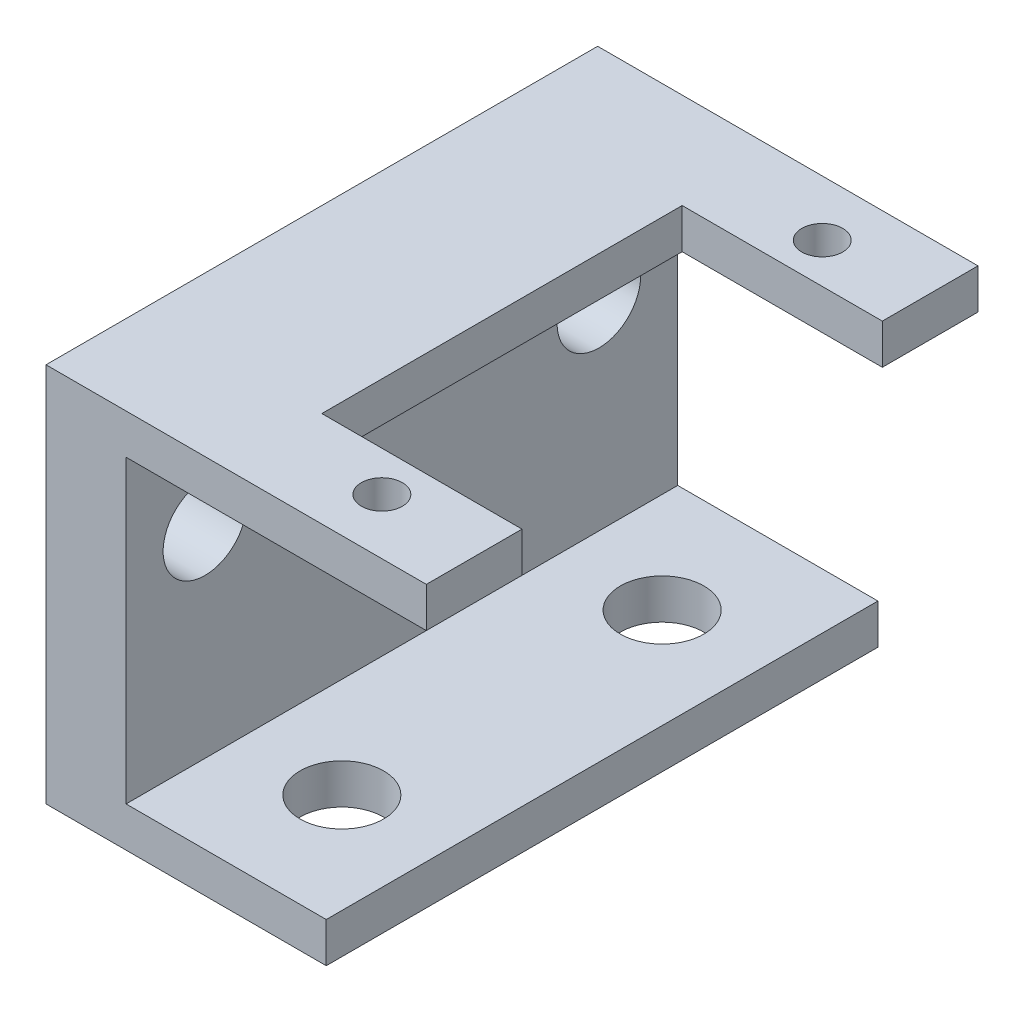
SolidWorks part; units mm, degrees
ref_plane "Front Plane" through (0, 0, 0) normal (0, 0, 1) x (1, 0, 0)
ref_plane "Top Plane" through (0, 0, 0) normal (0, 1, 0) x (1, 0, 0)
ref_plane "Right Plane" through (0, 0, 0) normal (1, 0, 0) x (0, 0, -1)
sketch "Sketch1" plane through (0, 0, 0) normal (0, 0, 1) x (1, 0, 0)
  line L1 (0, 0) -> (17.78, 0)
  line L2 (0, 0) -> (0, 2.54)
  line L3 (0, 2.54) -> (17.78, 2.54)
  line L4 (17.78, 0) -> (17.78, 2.54)
  line L5 (0, 2.54) -> (5.08, 2.54)
  line L6 (0, 2.54) -> (0, 21.59)
  line L7 (0, 21.59) -> (5.08, 21.59)
  line L8 (5.08, 2.54) -> (5.08, 21.59)
  line L9 (0, 21.59) -> (24.13, 21.59)
  line L10 (0, 21.59) -> (0, 24.13)
  line L11 (0, 24.13) -> (24.13, 24.13)
  line L12 (24.13, 21.59) -> (24.13, 24.13)
  dimension "D1" = 5.08
  dimension "D2" = 12.7
  dimension "D3" = 19.05
  dimension "D4" = 2.54
  dimension "D5" = 2.54
  dimension "D6" = 19.05
extrude "Boss-Extrude1" add sketch "Sketch1" along normal blind 35 contours L9 L12 L11 L10 L7 | L6 L5 L8 L7 | L2 L1 L4 L3 region at (12.065, 22.86, 0)
hole_wizard "Ø5.0mm Dowel Hole1" positions "Sketch2" profile "Sketch3" hole size "Ø5.0" standard "ANSI Metric" end condition through all
sketch "Sketch2" plane through (5.08, 0, 0) normal (1, 0, 0) x (0, 0, -1)
  line L3 (-35, 2.54) -> (0, 2.54) construction
  line L6 (-30, 15.24) -> (-5, 15.24) construction
  line L8 (-35, 0) -> (0, 0) construction
  point P0 (-30, 15.24)
  point P2 (-5, 15.24)
  point P30 (-17.5, 0)
  point P31 (-17.5, 15.24)
  dimension "D1" = 25
  dimension "D3" = 12.7
sketch "Sketch3" plane through (5.08, 15.24, 30) normal (0, 1, 0) x (0, 0, -1)
  line L0 (0, 0) -> (0, 5.08)
  line L1 (0, 5.08) -> (2.65, 5.08)
  line L2 (2.65, 5.08) -> (2.65, 0)
  line L5 (2.65, 0) -> (0, 0)
  line L11 (0, -6.35) -> (0, 107.95) construction
  dimension "Thru Hole Dia." = 5.3
  dimension "Thru Hole Depth" = 5.08
hole_wizard "Ø5.0mm Dowel Hole2" positions "Sketch4" profile "Sketch5" hole size "Ø5.0" standard "ANSI Metric" end condition through all
sketch "Sketch4" plane through (0, 2.54, 0) normal (0, 1, 0) x (1, 0, 0)
  line L2 (11.43, -7.34) -> (11.43, -27.66) construction
  line L5 (5.08, -35) -> (5.08, 0) construction
  line L6 (17.78, -35) -> (17.78, 0) construction
  point P0 (11.43, -27.66)
  point P2 (11.43, -7.34)
  point P19 (12.065, -27.38)
  point P20 (12.1197, -7.62)
  point P25 (17.78, -17.5)
  point P26 (11.43, -17.5)
  dimension "D1" = 20.32
  dimension "D2" = 6.35
sketch "Sketch5" plane through (11.43, 2.54, 27.66) normal (1, 0, 0) x (0, 0, 1)
  line L0 (0, 0) -> (0, 2.54)
  line L1 (0, 2.54) -> (2.65, 2.54)
  line L2 (2.65, 2.54) -> (2.65, 0)
  line L5 (2.65, 0) -> (0, 0)
  line L11 (0, -6.35) -> (0, 107.95) construction
  dimension "Thru Hole Dia." = 5.3
  dimension "Thru Hole Depth" = 2.54
sketch "Sketch6" plane through (0, 24.13, 0) normal (0, 1, 0) x (1, 0, 0)
  line L0 (24.13, -35) -> (24.13, 0) construction
  line L1 (24.13, -6.07) -> (11.43, -6.07)
  line L2 (24.13, -6.07) -> (24.13, -28.93)
  line L3 (24.13, -28.93) -> (11.43, -28.93)
  line L4 (11.43, -6.07) -> (11.43, -28.93)
  line L5 (0, 0) -> (24.13, 0) construction
  line L6 (0, -35) -> (24.13, -35) construction
  line L9 (17.78, -6.07) -> (17.78, 0) construction
  line L10 (17.78, -28.93) -> (17.78, -35) construction
  dimension "D2" = 12.7
  dimension "D1" = 22.86
extrude "Cut-Extrude1" cut sketch "Sketch6" against normal up to next contours L2 L1 L4 L3
hole_wizard "M2 Clearance Hole1" positions "Sketch7" profile "Sketch8" hole size "M2" standard "ANSI Metric" end condition up to next
sketch "Sketch7" plane through (0, 24.13, 0) normal (0, 1, 0) x (1, 0, 0)
  line L0 (17.78, -28.93) -> (17.78, -35) construction
  line L1 (17.78, -6.07) -> (17.78, 0) construction
  line L2 (11.43, -6.07) -> (11.43, -28.93) construction
  point P0 (17.78, -31.47)
  point P4 (17.78, -3.53)
  point P13 (11.43, -17.5)
  dimension "D1" = 13.97
  dimension "D2" = 13.97
sketch "Sketch8" plane through (17.78, 24.13, 31.47) normal (1, 0, 0) x (0, 0, 1)
  line L0 (0, 0) -> (0, 2.54)
  line L1 (0, 2.54) -> (1.3, 2.54)
  line L2 (1.3, 2.54) -> (1.3, 0)
  line L5 (1.3, 0) -> (0, 0)
  line L11 (0, -6.35) -> (0, 107.95) construction
  dimension "Thru Hole Dia." = 2.6
  dimension "Thru Hole Depth" = 2.54
equation "\"wall thicc\"= 2.5mm"
equation "\"press fit\"= 0.3mm"
equation "\"shaft thick\"= 5mm + \"press fit\""
equation "\"D1@Sketch1\"=\"wall thicc\"*2"
equation "\"D4@Sketch1\"=\"wall thicc\""
equation "\"D5@Sketch1\"=\"wall thicc\""
equation "\"servo width\"= 22.5mm"
equation "\"D1@Sketch6\"=\"servo width\"+\"press fit\""
equation "\"servo length\"= 12.5mm"
equation "\"D2@Sketch6\"=\"servo length\"+\"press fit\""
equation "\"servo hole spacing\"= 13.9mm"
equation "\"D1@Sketch7\"=\"servo hole spacing\""
equation "\"D2@Sketch7\"=\"servo hole spacing\""
